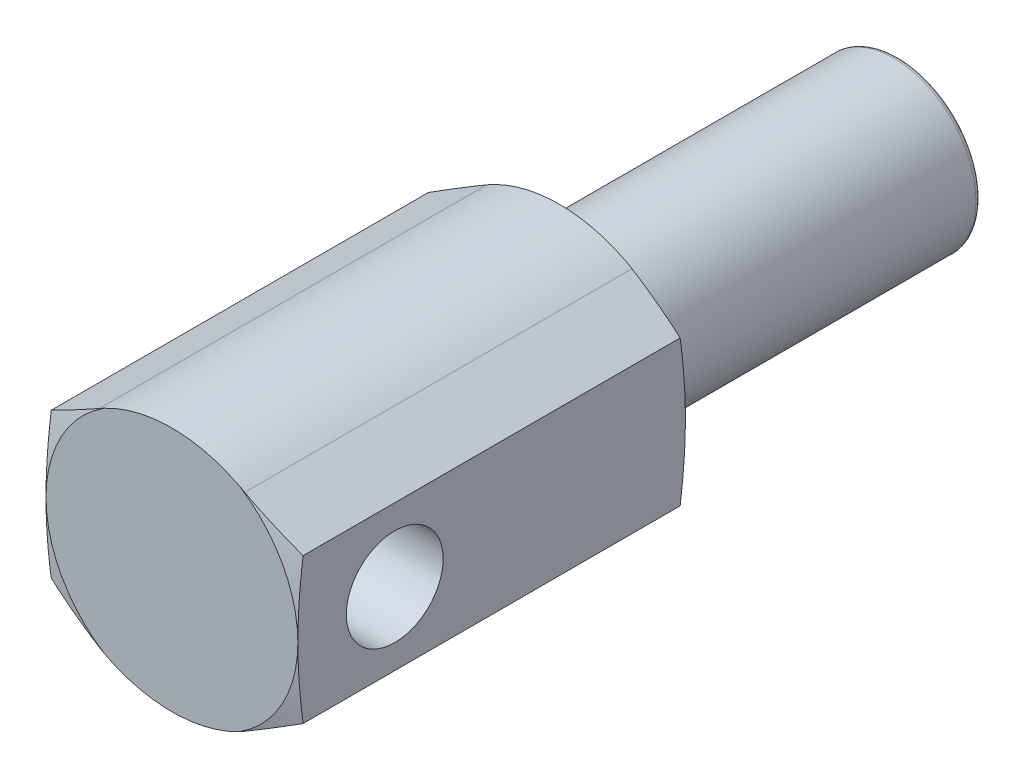
SolidWorks part; units mm, degrees
ref_plane "Plano frontal" through (0, 0, 0) normal (0, 0, 1) x (1, 0, 0)
ref_plane "Plano superior" through (0, 0, 0) normal (0, 1, 0) x (1, 0, 0)
ref_plane "Plano direito" through (0, 0, 0) normal (1, 0, 0) x (0, 0, -1)
sketch "Esboço1" plane through (0, 0, 0) normal (0, 0, 1) x (1, 0, 0)
  line L1 (0, 15.0111) -> (-13, 7.5056)
  line L2 (-13, 7.5056) -> (-13, -7.5056)
  line L3 (-13, -7.5056) -> (0, -15.0111)
  line L4 (0, -15.0111) -> (13, -7.5056)
  line L5 (13, -7.5056) -> (13, 7.5056)
  line L6 (13, 7.5056) -> (0, 15.0111)
  circle A0 centre (0, 0) radius 13 construction
  dimension "D1" = 26
extrude "Ressalto-extrusão1" add sketch "Esboço1" along normal blind 40
sketch "Esboço2" plane through (0, 0, 40) normal (0, 0, 1) x (1, 0, 0)
  circle A0 centre (0, 0) radius 13
extrude "Corte-extrusão1" cut sketch "Esboço2" against normal blind 15 draft 75 flip side to cut
sketch "Esboço3" plane through (0, 0, 0) normal (0, 0, -1) x (-1, 0, 0)
  circle A0 centre (0, 0) radius 13
extrude "Corte-extrusão2" cut sketch "Esboço3" against normal blind 15 draft 75 flip side to cut
sketch "Esboço4" plane through (0, 0, 0) normal (0, 0, -1) x (-1, 0, 0)
  circle A0 centre (0, 0) radius 8.5
  dimension "D1" = 17
extrude "Ressalto-extrusão2" add sketch "Esboço4" along normal blind 35
fillet "Filete1" radius 0.5 1 edges at (-8.5, 0, -35)
hole_wizard "Furo roscado de M61" positions "Esboço5" profile "Esboço6" tap size "M6" standard "DIN"
sketch "Esboço5" plane through (0, 0, -35) normal (0, 0, -1) x (-1, 0, 0)
  point P0 (0, 0)
sketch "Esboço6" plane through (0, 0, -35) normal (1, 0, 0) x (0, 1, 0)
  line L0 (0, 0) -> (0, 18.5022)
  line L1 (0, 18.5022) -> (2.5, 17)
  line L2 (2.5, 17) -> (2.5, 0)
  line L5 (2.5, 0) -> (0, 0)
  line L10 (0, 18.5022) -> (-2.5, 17) construction
  line L11 (0, -6.35) -> (0, 107.95) construction
  dimension "Tap Drill Dia." = 5
  dimension "Tap Drill Depth" = 17
  dimension "Drill Angle" = 118
cosmetic thread "Rosca de furo1" parameters "D1"=12, "D2"=6
cosmetic thread "Representação de rosca1" parameters "D1"=15, "D2"=6
sketch "Esboço7" plane through (-13, 0, 0) normal (-1, 0, 0) x (0, 0, 1)
  circle A0 centre (30, 0) radius 5
  dimension "D1" = 10
  dimension "D2" = 10
extrude "Corte-extrusão3" cut sketch "Esboço7" against normal through all contours A0
fillet "Filete2" radius 15 1 edges at (0, 15.0111, 20)
fillet "Filete3" radius 15 1 edges at (0, -15.0111, 20)
